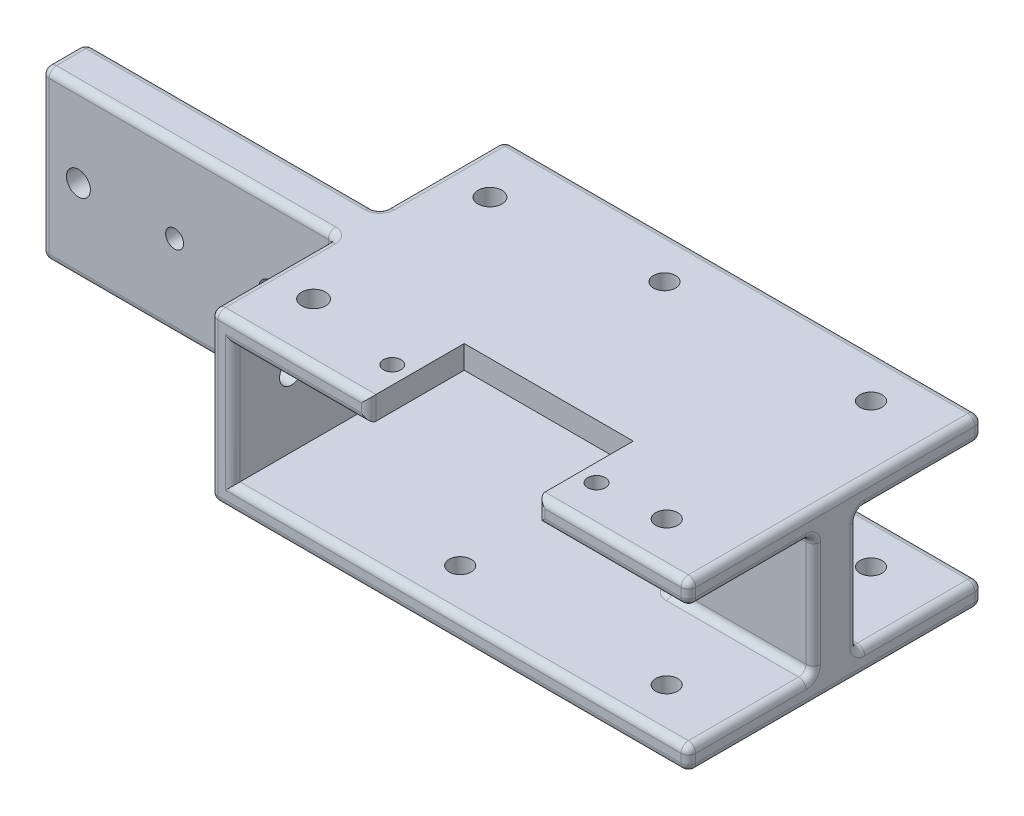
SolidWorks part; units mm, degrees
material "Delrin 2700 NC010, Low Viscosity Acetal Copolymer (SS)"
ref_plane "Front Plane" through (0, 0, 0) normal (0, 0, 1) x (1, 0, 0)
ref_plane "Top Plane" through (0, 0, 0) normal (0, 1, 0) x (1, 0, 0)
ref_plane "Right Plane" through (0, 0, 0) normal (1, 0, 0) x (0, 0, -1)
sketch "Sketch1" plane through (0, 0, 0) normal (0, 1, 0) x (1, 0, 0)
  line L1 (0, 20) -> (65, 20)
  line L2 (0, 20) -> (0, -20)
  line L3 (0, -20) -> (65, -20)
  line L4 (65, 20) -> (65, -20)
  point P4 (0, 0)
  dimension "D1" = 65
  dimension "D2" = 40
extrude "Boss-Extrude1" add sketch "Sketch1" against normal blind 3.15
extrude "Boss-Extrude2" add sketch "Sketch1<2>" along normal blind 3.15 from offset 16.4 separate body
sketch "Sketch1<2>" plane through (0, 0, 0) normal (0, 1, 0) x (1, 0, 0) same geometry as "Sketch1"
sketch "Sketch2" plane through (0, 0, 0) normal (0, 1, 0) x (1, 0, 0)
  line L0 (0, -20) -> (65, -20) construction
  line L1 (0, 20) -> (3, 20)
  line L2 (0, 20) -> (0, -20)
  line L3 (0, -20) -> (3, -20)
  line L4 (3, 20) -> (3, -20)
  line L5 (65, -20) -> (65, 20) construction
  line L6 (65, 3) -> (45, 3)
  line L7 (65, 3) -> (65, -3)
  line L8 (65, -3) -> (45, -3)
  line L9 (45, 3) -> (45, -3)
  point P14 (65, 0)
  dimension "D2" = 6
  dimension "D3" = 20
extrude "Boss-Extrude3" add sketch "Sketch2" along normal up to surface (16.4 mm away) up to face at (32.5, 16.4, 0)
sketch "Sketch3" plane through (0, 0, 0) normal (-1, 0, 0) x (0, 0, 1)
  line L0 (-20, 19.55) -> (20, 19.55) construction
  line L1 (-3, 19.55) -> (3, 19.55)
  line L2 (-3, 19.55) -> (-3, -3.15)
  line L3 (-3, -3.15) -> (3, -3.15)
  line L4 (3, 19.55) -> (3, -3.15)
  line L5 (-20, -3.15) -> (20, -3.15) construction
  point P8 (0, 19.55)
  dimension "D3" = 6
extrude "Boss-Extrude4" add sketch "Sketch3" along normal blind 40
hole_wizard "M2 Clearance Hole1" positions "Sketch7" profile "Sketch9" hole size "M2" standard "ANSI Metric"
sketch "Sketch7" plane through (0, 19.55, 0) normal (0, 1, 0) x (1, 0, 0)
  line L1 (0, -20) -> (65, -20) construction
  line L2 (65, -20) -> (65, 20) construction
  point P0 (19.1, -14.4)
  point P2 (46.9, -14.4)
  point P5 (19.1, -14.4)
  point P7 (46.9, -14.4)
  dimension "D1" = 27.8
  dimension "D3" = 5.6
  dimension "D2" = 18.1
sketch "Sketch9" plane through (19.1, 19.55, 14.4) normal (1, 0, 0) x (0, 0, 1)
  line L0 (0, 0) -> (0, 5.721)
  line L1 (0, 5.721) -> (1.2, 5)
  line L2 (1.2, 5) -> (1.2, 0)
  line L5 (1.2, 0) -> (0, 0)
  line L10 (0, 5.721) -> (-1.2, 5) construction
  line L11 (0, -6.35) -> (0, 107.95) construction
  dimension "Hole Dia." = 2.4
  dimension "Hole Depth" = 5
  dimension "Drill Angle" = 118
hole_wizard "Ø3.0mm Dowel Hole1" positions "Sketch10" profile "Sketch11" hole size "Ø3.0" standard "ANSI Metric" end condition through all
sketch "Sketch10" plane through (0, 19.55, 0) normal (0, 1, 0) x (1, 0, 0)
  line L0 (0, -20) -> (65, -20) construction
  line L1 (65, -20) -> (65, 20) construction
  point P0 (55.95, -13.9)
  point P7 (27.85, 13.9)
  point P13 (55.95, 13.9)
  point P14 (27.85, -13.9)
  point P16 (0, 0)
  dimension "D1" = 6.1
  dimension "D2" = 9.05
  dimension "D4" = 37.15
  dimension "D3" = 27.8
sketch "Sketch11" plane through (55.95, 19.55, 13.9) normal (1, 0, 0) x (0, 0, 1)
  line L0 (0, 0) -> (0, 22.7)
  line L1 (0, 22.7) -> (1.5, 22.7)
  line L2 (1.5, 22.7) -> (1.5, 0)
  line L5 (1.5, 0) -> (0, 0)
  line L11 (0, -6.35) -> (0, 107.95) construction
  dimension "Thru Hole Dia." = 3
  dimension "Thru Hole Depth" = 22.7
sketch "Sketch5" plane through (0, 19.55, 0) normal (0, 1, 0) x (1, 0, 0)
  line L0 (0, -20) -> (65, -20) construction
  line L1 (21.5, -20) -> (44.5, -20)
  line L2 (21.5, -20) -> (21.5, -7)
  line L3 (21.5, -7) -> (44.5, -7)
  line L4 (44.5, -20) -> (44.5, -7)
  circle A0 centre (46.9, -14.4) radius 1.2 construction
  point P6 (33, -7)
  dimension "D1" = 23
  dimension "D2" = 13.9
  dimension "D3" = 13
extrude "Cut-Extrude1" cut sketch "Sketch5" against normal blind 7
fillet "Fillet1" radius 1 48 edges at (0, -3.15, 11.5) (0, 19.55, -11.5) (3, 8.2, -20) (34, 16.4, -20) (32.5, 19.55, -20) (32.5, -3.15, -20) (34, 0, -20) (-20, -3.15, 3) (-20, 19.55, 3) (0, 8.2, 3) (65, 8.2, 3) (65, 16.4, 11.5) (65, 19.55, 0) (65, 17.975, -20) (65, 16.4, -11.5) (65, 8.2, -3) (65, 0, -11.5) (65, -1.575, -20) (65, -3.15, 0) (65, 0, 11.5) (54.75, 19.55, 20) (65, 17.975, 20) (54.75, 16.4, 20) (44.5, 17.975, 20) (12.25, 16.4, 20) (3, 8.2, 20) (34, 0, 20) (65, -1.575, 20) (32.5, -3.15, 20) (0, 8.2, 20) (10.75, 19.55, 20) (21.5, 17.975, 20) (-40, 19.55, 0) (-40, 8.2, 3) (-40, -3.15, 0) (0, 8.2, -20) (-20, 19.55, -3) (-40, 8.2, -3) (-20, -3.15, -3) (0, 8.2, -3) (55, 0, -3) (55, 16.4, -3) (45, 0, 0) (45, 8.2, -3) (45, 16.4, 0) (55, 0, 3) (45, 8.2, 3) (55, 16.4, 3)
hole_wizard "#4 Clearance Hole1" positions "Sketch14" profile "Sketch15" hole size "#4" standard "ANSI Inch" end condition through all
sketch "Sketch14" plane through (0, 0, 3) normal (0, 0, 1) x (1, 0, 0)
  line L0 (-40, -2.15) -> (-40, 18.55) construction
  point P0 (-35, 8.2)
  point P2 (-8.82, 8.2)
  point P7 (-40, 8.2)
  dimension "D1" = 26.18
  dimension "D2" = 5
sketch "Sketch15" plane through (-35, 8.2, 3) normal (1, 0, 0) x (0, -1, 0)
  line L0 (0, 0) -> (0, 23)
  line L1 (0, 23) -> (1.6319, 23)
  line L2 (1.6319, 23) -> (1.6319, 0)
  line L5 (1.6319, 0) -> (0, 0)
  line L11 (0, -6.35) -> (0, 107.95) construction
  dimension "Thru Hole Dia." = 3.2639
  dimension "Thru Hole Depth" = 23
hole_wizard "#2 Clearance Hole1" positions "Sketch16" profile "Sketch17" hole size "#2" standard "ANSI Inch" end condition through all
sketch "Sketch16" plane through (0, 0, 3) normal (0, 0, 1) x (1, 0, 0)
  line L0 (-40, -2.15) -> (-40, 18.55) construction
  circle A0 centre (-35, 8.2) radius 1.632 construction
  point P0 (-21.91, 8.2)
  point P8 (-40, 8.2)
  dimension "D1" = 13.09
sketch "Sketch17" plane through (-21.91, 8.2, 3) normal (1, 0, 0) x (0, -1, 0)
  line L0 (0, 0) -> (0, 23)
  line L1 (0, 23) -> (1.2192, 23)
  line L2 (1.2192, 23) -> (1.2192, 0)
  line L5 (1.2192, 0) -> (0, 0)
  line L11 (0, -6.35) -> (0, 107.95) construction
  dimension "Thru Hole Dia." = 2.4384
  dimension "Thru Hole Depth" = 23
hole_wizard "#4 Clearance Hole2" positions "Sketch18" profile "Sketch19" hole size "#4" standard "ANSI Inch"
sketch "Sketch18" plane through (0, 19.55, 0) normal (0, 1, 0) x (1, 0, 0)
  point P0 (6, 12)
  point P2 (6, -12)
  dimension "D1" = 12
  dimension "D2" = 12
  dimension "D3" = 6
sketch "Sketch19" plane through (6, 19.55, -12) normal (1, 0, 0) x (0, 0, 1)
  line L0 (0, 0) -> (0, 10.9806)
  line L1 (0, 10.9806) -> (1.6319, 10)
  line L2 (1.6319, 10) -> (1.6319, 0)
  line L5 (1.6319, 0) -> (0, 0)
  line L10 (0, 10.9806) -> (-1.632, 10) construction
  line L11 (0, -6.35) -> (0, 107.95) construction
  dimension "Hole Dia." = 3.2639
  dimension "Hole Depth" = 10
  dimension "Drill Angle" = 118
hole_wizard "#4 Clearance Hole3" positions "Sketch20" profile "Sketch21" hole size "#4" standard "ANSI Inch" end condition through all
sketch "Sketch20" plane through (0, 0, 0) normal (-1, 0, 0) x (0, 0, 1)
  line L0 (4, 19.55) -> (19, 19.55) construction
  point P0 (-12, 9.55)
  point P2 (12, 9.55)
  point P15 (0, 0)
  dimension "D2" = 12
  dimension "D1" = 10
  dimension "D3" = 12
sketch "Sketch21" plane through (0, 9.55, -12) normal (0, 1, 0) x (0, 0, 1)
  line L0 (0, 0) -> (0, 65)
  line L1 (0, 65) -> (1.6319, 65)
  line L2 (1.6319, 65) -> (1.6319, 0)
  line L5 (1.6319, 0) -> (0, 0)
  line L11 (0, -6.35) -> (0, 107.95) construction
  dimension "Thru Hole Dia." = 3.2639
  dimension "Thru Hole Depth" = 65
equation "\"D2@Sketch7\"=9.05*2"
equation "\"D1@Sketch10\"=(40-\"D3@Sketch10\")/2"
equation "\"D3@Sketch7\"=5.6"
equation "\"D2@Sketch18\"=\"D1@Sketch18\""
equation "\"D3@Sketch20\"=\"D2@Sketch20\""
